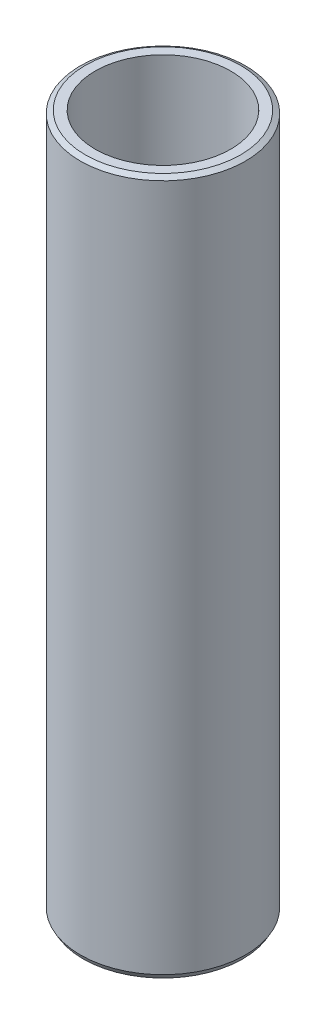
SolidWorks part; units mm, degrees
ref_plane "Front Plane" through (0, 0, 0) normal (0, 0, 1) x (1, 0, 0)
ref_plane "Top Plane" through (0, 0, 0) normal (0, 1, 0) x (1, 0, 0)
ref_plane "Right Plane" through (0, 0, 0) normal (1, 0, 0) x (0, 0, -1)
sketch "Sketch1" plane through (0, 0, 0) normal (0, 1, 0) x (1, 0, 0)
  circle A0 centre (0, 0) radius 37.5
  dimension "SHAFT_OD" = 75
extrude "Boss-Extrude1" add sketch "Sketch1" along normal blind 315.7483
sketch "Sketch2" plane through (0, 0, 0) normal (0, 1, 0) x (1, 0, 0)
  circle A0 centre (0, 0) radius 30.7842
  dimension "BORE_D" = 61.5684
extrude "Cut-Extrude1" cut sketch "Sketch2" along normal through all
chamfer "Chamfer1" distance 1.3053 angle 60 2 edges at (0, 315.7483, 37.5) (0, 0, 37.5) first distance on face at (0, 315.7483, 37.5) first distance on face at (0, 0, 30.7842)
